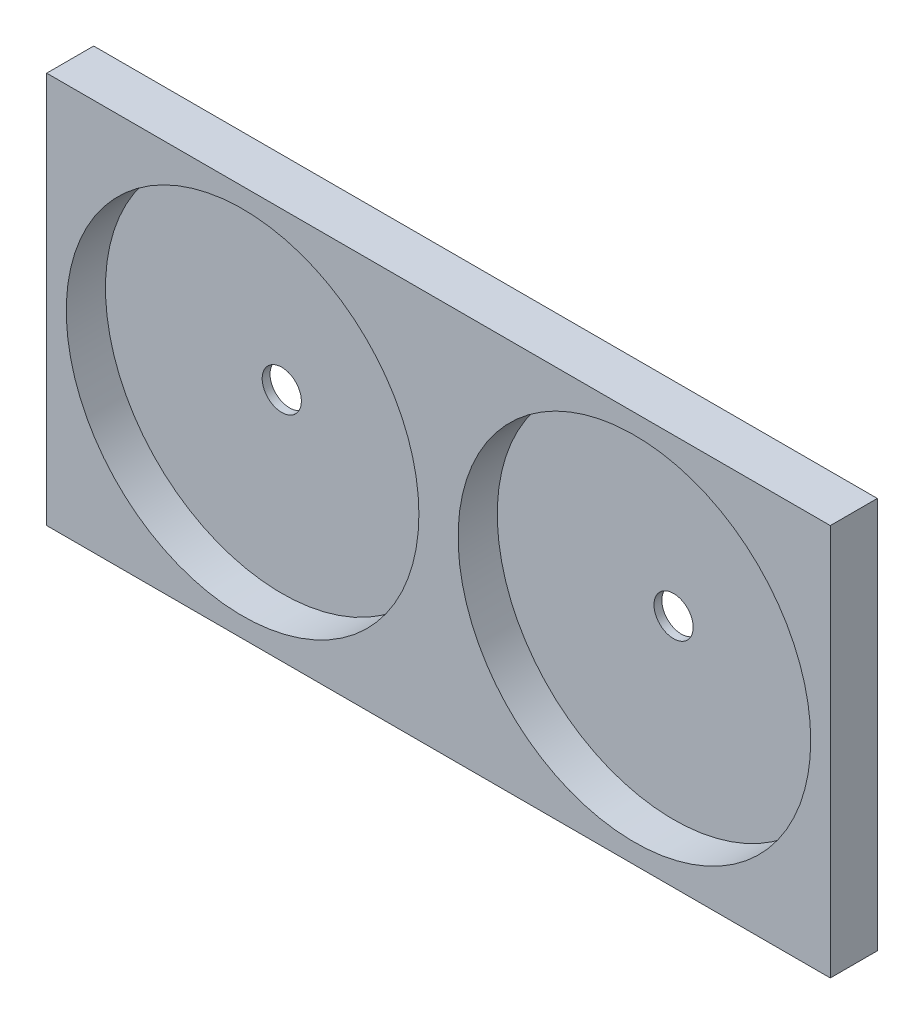
SolidWorks part; units mm, degrees
ref_plane "Front Plane" through (0, 0, 0) normal (0, 0, 1) x (1, 0, 0)
ref_plane "Top Plane" through (0, 0, 0) normal (0, 1, 0) x (1, 0, 0)
ref_plane "Right Plane" through (0, 0, 0) normal (1, 0, 0) x (0, 0, -1)
sketch "Sketch1" plane through (0, 0, 0) normal (0, 0, 1) x (1, 0, 0)
  line L1 (0, 0) -> (200, 0)
  line L2 (0, 0) -> (0, 100)
  line L3 (0, 100) -> (200, 100)
  line L4 (200, 0) -> (200, 100)
  dimension "D1" = 200
  dimension "D2" = 100
extrude "Boss-Extrude1" add sketch "Sketch1" along normal blind 12
sketch "Sketch2" plane through (0, 0, 12) normal (0, 0, 1) x (1, 0, 0)
  line L0 (0, 50) -> (200, 50) construction
  line L1 (0, 100) -> (0, 0) construction
  line L2 (200, 0) -> (200, 100) construction
  circle A0 centre (50, 50) radius 45
  circle A1 centre (150, 50) radius 45
  point P10 (45.2908, 50)
  point P11 (150.5008, 50)
  point P12 (100, 50)
  dimension "D1" = 90
  dimension "D2" = 90
  dimension "D3" = 50
  dimension "D4" = 50
extrude "Cut-Extrude1" cut sketch "Sketch2" against normal blind 10
sketch "Sketch3" plane through (0, 0, 12) normal (0, 0, 1) x (1, 0, 0)
  circle A0 centre (50, 50) radius 5
  circle A1 centre (150, 50) radius 5
  circle A2 centre (150, 50) radius 45 construction
  circle A4 centre (50, 50) radius 45 construction
  dimension "D1" = 10
extrude "Cut-Extrude2" cut sketch "Sketch3" against normal through all
sketch "Sketch4" plane through (0, 0, 0) normal (0, 0, -1) x (-1, 0, 0)
  line L0 (-150, 55.2961) -> (-150, 25.3943) construction
  line L1 (-133.6003, 55.2961) -> (-133.6003, 25.3943)
  line L2 (-166.3997, 55.2961) -> (-166.3997, 25.3943)
  line L3 (-50, 55.2961) -> (-50, 25.3943) construction
  line L6 (-141.6003, 55.2961) -> (-141.6003, 25.3943)
  line L7 (-158.3997, 55.2961) -> (-158.3997, 25.3943)
  line L8 (-33.6003, 55.2961) -> (-33.6003, 25.3943)
  line L9 (-66.3997, 55.2961) -> (-66.3997, 25.3943)
  line L10 (-41.6003, 55.2961) -> (-41.6003, 25.3943)
  line L13 (-58.3997, 55.2961) -> (-58.3997, 25.3943)
  arc A0 (-133.6003, 55.2961) -> (-166.3997, 55.2961) centre (-150, 55.2961) ccw
  arc A1 (-166.3997, 25.3943) -> (-133.6003, 25.3943) centre (-150, 25.3943) ccw
  arc A4 (-158.3997, 25.3943) -> (-141.6003, 25.3943) centre (-150, 25.3943) ccw
  arc A5 (-141.6003, 55.2961) -> (-158.3997, 55.2961) centre (-150, 55.2961) ccw
  arc A6 (-33.6003, 55.2961) -> (-66.3997, 55.2961) centre (-50, 55.2961) ccw
  arc A7 (-66.3997, 25.3943) -> (-33.6003, 25.3943) centre (-50, 25.3943) ccw
  circle A10 centre (-50, 50) radius 3 construction
  arc A11 (-58.3997, 25.3943) -> (-41.6003, 25.3943) centre (-50, 25.3943) ccw
  arc A12 (-41.6003, 55.2961) -> (-58.3997, 55.2961) centre (-50, 55.2961) ccw
  circle A13 centre (-50, 50) radius 3 construction
  circle A14 centre (-150, 50) radius 3 construction
  circle A15 centre (-150, 50) radius 3 construction
  point P2 (-150, 40.3452)
  point P9 (-50, 40.3452)
  point P16 (0, 0)
  dimension "D1" = 8
  dimension "D2" = 8
extrude "Cut-Extrude4" cut sketch "Sketch4" against normal blind 1.5
sketch "Sketch5" plane through (0, 0, 0) normal (0, 0, -1) x (-1, 0, 0)
  line L0 (-110.12, 30.25) -> (-89.8, 30.25) construction
  line L1 (-110.12, 32.25) -> (-89.8, 32.25)
  line L2 (-110.12, 28.25) -> (-89.8, 28.25)
  line L3 (-110.12, 15) -> (-89.8, 15) construction
  line L4 (-110.12, 17) -> (-89.8, 17)
  line L5 (-110.12, 13) -> (-89.8, 13)
  arc A0 (-110.12, 32.25) -> (-110.12, 28.25) centre (-110.12, 30.25) ccw
  arc A1 (-89.8, 28.25) -> (-89.8, 32.25) centre (-89.8, 30.25) ccw
  arc A2 (-110.12, 17) -> (-110.12, 13) centre (-110.12, 15) ccw
  arc A3 (-89.8, 13) -> (-89.8, 17) centre (-89.8, 15) ccw
  circle A4 centre (-110.12, 30.25) radius 0.5 construction
  circle A5 centre (-110.12, 30.25) radius 0.5 construction
  circle A6 centre (-89.8, 30.25) radius 0.5 construction
  circle A7 centre (-89.8, 30.25) radius 0.5 construction
  circle A8 centre (-89.8, 15) radius 0.5 construction
  circle A9 centre (-89.8, 15) radius 0.5 construction
  circle A10 centre (-110.12, 15) radius 0.5 construction
  circle A11 centre (-110.12, 15) radius 0.5 construction
  point P2 (-99.96, 30.25)
  point P7 (-99.96, 15)
  point P14 (-110.0997, 30.2291)
  point P15 (-89.9783, 30.147)
  point P16 (-90.43, 31.7074)
  point P17 (-101.1067, 34.7872)
  point P30 (-110.12, 30.25)
  point P31 (-89.8, 30.25)
  point P32 (0, 0)
  point P33 (0, 0)
  point P34 (-110.12, 15)
  point P36 (-89.8, 15)
  dimension "D1" = 4
extrude "Cut-Extrude5" cut sketch "Sketch5" against normal blind 1.5
